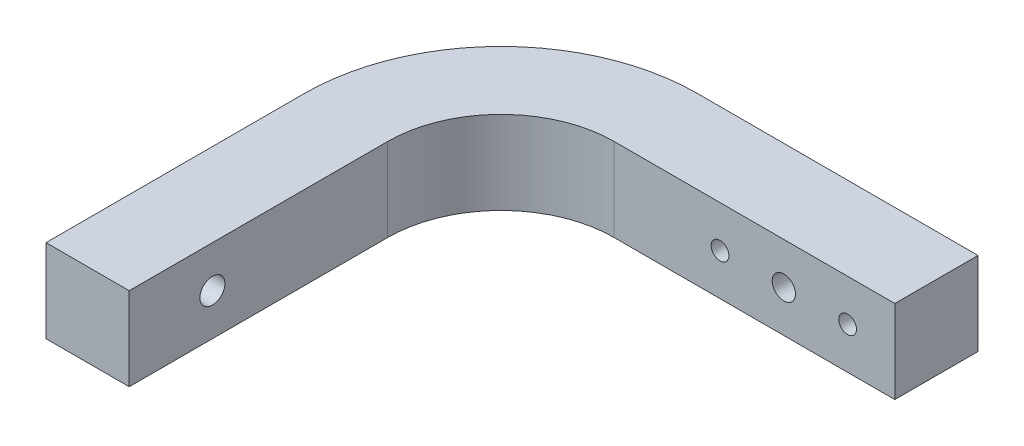
SolidWorks part; units mm, degrees
ref_plane "Front Plane" through (0, 0, 0) normal (0, 0, 1) x (1, 0, 0)
ref_plane "Top Plane" through (0, 0, 0) normal (0, 1, 0) x (1, 0, 0)
ref_plane "Right Plane" through (0, 0, 0) normal (1, 0, 0) x (0, 0, -1)
ref_axis "Z" through (0, 0, -59.2654) along (0, 0, 1)
sketch "Sketch1" plane through (0, 0, 0) normal (0, 1, 0) x (1, 0, 0)
  line L0 (-30.6, 0) -> (30.6, 0) construction
  line L1 (-66, -35.4) -> (-66, -82)
  line L2 (-66, -82) -> (-51, -82)
  line L3 (-51, -82) -> (-51, -35.4)
  line L4 (-30.6, -15) -> (30.6, -15) construction
  line L5 (0, -15) -> (0, 0) construction
  line L6 (51, -82) -> (51, -35.4) construction
  line L7 (66, -82) -> (51, -82) construction
  line L8 (66, -35.4) -> (66, -82) construction
  line L9 (30.6, 0) -> (30.6, -15) construction
  line L10 (20, -15) -> (20, 0)
  line L11 (-30.6, -15) -> (20, -15)
  line L12 (-30.6, 0) -> (20, 0)
  line L13 (0, 59.2654) -> (0, -30.9346) construction
  arc A0 (-30.6, 0) -> (-66, -35.4) centre (-30.6, -35.4) ccw
  arc A1 (-51, -35.4) -> (-30.6, -15) centre (-30.6, -35.4) cw
  arc A2 (51, -35.4) -> (30.6, -15) centre (30.6, -35.4) ccw construction
  arc A3 (30.6, 0) -> (66, -35.4) centre (30.6, -35.4) cw construction
  dimension "D3" = 20.4
  dimension "D1" = 102
  dimension "D2" = 15
  dimension "D4" = 67
  dimension "D5" = 20
extrude "Boss-Extrude1" add sketch "Sketch1" along normal blind 7.5 and the other way blind 7.5
sketch "Sketch2" plane through (-51, 0, 0) normal (-1, 0, 0) x (0, 0, 1)
  line L1 (45.1, 0) -> (-45.1, 0) construction
  line L2 (0, -8.25) -> (0, 8.25) construction
  circle A0 centre (67, 0) radius 2.25
  dimension "D1" = 4.5
  dimension "D2" = 67
extrude "Cut-Extrude1" cut sketch "Sketch2" against normal through all both and the other way through all
ref_axis "Axis2" through (-92.6767, 0, 67) along (1, 0, 0)
sketch "Sketch3" plane through (0, 0, 0) normal (0, 0, -1) x (-1, 0, 0)
  line L0 (-11.5, 0) -> (11.5, 0) construction
  circle A0 centre (0, 0) radius 2.1
  circle A1 centre (-11.5, 0) radius 1.6
  circle A2 centre (11.5, 0) radius 1.6
  dimension "D1" = 4.2
  dimension "D3" = 3.2
  dimension "D2" = 23
extrude "Cut-Extrude2" cut sketch "Sketch3" against normal through all
equation "\"width\"= \"EyeDiameter\" + \"EyeClearance\""
equation "\"prongwidth\"= \"L2Thickness\""
equation "\"D2@Sketch1\"=\"prongwidth\""
equation "\"D3@Sketch1\"=\"width\"/5"
equation "\"pronglength\"= \"BasePlaneDistance\"'model implicitly adds clearance (of prongwidth) to the hole drilled at the baseplanedistance"
equation "\"D4@Sketch1\"=\"pronglength\""
equation "\"D1@Boss-Extrude1\"=\"prongwidth\"/2"
equation "\"D2@Boss-Extrude1\"=\"prongwidth\"/2"
equation "\"lbracket-plane-to-axis\"= \"BasePlaneDistance\""
equation "\"D2@Sketch2\"=\"lbracket-plane-to-axis\""
equation "\"EyeDiameter\" = 100"
equation "\"BasePlaneDistance\" = \"EyeDiameter\"/2+\"L2Thickness\"+\"EyeClearance\""
equation "\"EyeClearance\" = 2"
equation "\"D1@Sketch1\"=\"EyeDiameter\"+\"EyeClearance\""
equation "\"BearingDepth\"= 6"
equation "\"BearingHousingID\"=4.5"
equation "\"BearingFlangeThickness\"= 0.75"
equation "\"BearingFlangeOD\"=7.5"
equation "\"PrinterFilamentThickness\"= 0.1"
equation "\"ApplyPrinterOffset\"= 1'if 1, adjust hole sizes to try and make pressfits work with the 3d printer"
equation "\"L2Thickness\" = 15"
equation "\"L2_ID\" = 20"
equation "\"vx\" = 0"
equation "\"vy\" = 0"
equation "\"vz\" = 100"
equation "\"parametric_end\" = 1"
equation "\"Rw_3_xx\" = -(\"vz\")/sqr((\"vx\")^2 + (\"vz\")^2)"
equation "\"Rw_3_xy\" = 0"
equation "\"Rw_3_xz\" = (\"vx\")/sqr((\"vx\")^2 + (\"vz\")^2)"
equation "\"Rw_3_zx\" = (\"vx\")/sqr((\"vx\")^2 + (\"vy\")^2 + (\"vz\")^2)"
equation "\"Rw_3_zy\" = (\"vy\")/sqr((\"vx\")^2 + (\"vy\")^2 + (\"vz\")^2)"
equation "\"Rw_3_zz\" = (\"vz\")/sqr((\"vx\")^2 + (\"vy\")^2 + (\"vz\")^2)"
equation "\"Rw_3_yx\" = (\"vx\")*(\"vy\")/sqr((\"vx\")^4 + (\"vx\")^2*(\"vy\")^2 + 2*(\"vx\")^2*(\"vz\")^2 + (\"vy\")^2*(\"vz\")^2 + (\"vz\")^4)"
equation "\"Rw_3_yy\" = -sqr((\"vx\")^2 + (\"vz\")^2)/sqr((\"vx\")^2 + (\"vy\")^2 + (\"vz\")^2)"
equation "\"Rw_3_yz\" = (\"vy\")*(\"vz\")/sqr((\"vx\")^4 + (\"vx\")^2*(\"vy\")^2 + 2*(\"vx\")^2*(\"vz\")^2 + (\"vy\")^2*(\"vz\")^2 + (\"vz\")^4)"
equation "\"O2Targx\" = -\"BasePlaneDistance\"*(\"vx\")*(\"vy\")/sqr((\"vx\")^4 + (\"vx\")^2*(\"vy\")^2 + 2*(\"vx\")^2*(\"vz\")^2 + (\"vy\")^2*(\"vz\")^2 + (\"vz\")^4)"
equation "\"O2Targy\" = \"BasePlaneDistance\"*sqr((\"vx\")^2 + (\"vz\")^2)/sqr((\"vx\")^2 + (\"vy\")^2 + (\"vz\")^2)"
equation "\"O2Targz\" = -\"BasePlaneDistance\"*(\"vy\")*(\"vz\")/sqr((\"vx\")^4 + (\"vx\")^2*(\"vy\")^2 + 2*(\"vx\")^2*(\"vz\")^2 + (\"vy\")^2*(\"vz\")^2 + (\"vz\")^4)"
equation "\"O2Targx_0\" = -(\"BasePlaneDistance\")*sqr((\"vx\")^2 + (\"vz\")^2)/sqr((\"vx\")^2 + (\"vy\")^2 + (\"vz\")^2)"
equation "\"O2Targy_0\" = -(\"BasePlaneDistance\")*(\"vy\")*(\"vz\")/sqr((\"vx\")^4 + (\"vx\")^2*(\"vy\")^2 + 2*(\"vx\")^2*(\"vz\")^2 + (\"vy\")^2*(\"vz\")^2 + (\"vz\")^4)"
equation "\"O2Targz_0\" = (\"BasePlaneDistance\")*(\"vx\")*(\"vy\")/sqr((\"vx\")^4 + (\"vx\")^2*(\"vy\")^2 + 2*(\"vx\")^2*(\"vz\")^2 + (\"vy\")^2*(\"vz\")^2 + (\"vz\")^4) + (\"BasePlaneDistance\")"
equation "\"theta2_s1\" = arcsin(((\"BasePlaneDistance\") - (\"O2Targz_0\"))/(\"BasePlaneDistance\")) + pi"
equation "\"theta2_s2\" = -arcsin(((\"BasePlaneDistance\") - (\"O2Targz_0\"))/(\"BasePlaneDistance\"))"
equation "\"theta1_s1\" = arcsin((\"O2Targy_0\")/((\"BasePlaneDistance\")*cos((\"Theta2\")))) + pi"
equation "\"theta1_s2\" = -arcsin((\"O2Targy_0\")/((\"BasePlaneDistance\")*cos((\"Theta2\"))))"
equation "\"theta1_s3\" = -arccos(-(\"O2Targx_0\")/((\"BasePlaneDistance\")*cos((\"Theta2\")))) + 2*pi"
equation "\"theta1_s4\" = arccos(-(\"O2Targx_0\")/((\"BasePlaneDistance\")*cos((\"Theta2\"))))"
equation "\"Theta1\" = \"theta1_s2\" 'so far, theta1_s1 and theta1_s4 have agreed, and they agree with the sw constraint solver"
equation "\"Theta2\" = \"theta2_s2\""
equation "\"o2_x\" = -(\"BasePlaneDistance\")*cos((\"Theta1\"))*cos((\"Theta2\"))"
equation "\"o2_y\" = -(\"BasePlaneDistance\")*sin((\"Theta1\"))*cos((\"Theta2\"))"
equation "\"o2_z\" = (\"BasePlaneDistance\")*(sin((\"Theta2\")) + 1)"
equation "\"o1_x\" = (\"BasePlaneDistance\")*sin((\"Theta1\"))"
equation "\"o1_y\" = -(\"BasePlaneDistance\")*cos((\"Theta1\"))"
equation "\"o1_z\" = (\"BasePlaneDistance\")"
equation "\"Actuator1_Theta\" = atn(\"vx\"/\"vz\") 'ik solution for the single link joint"
equation "\"Actuator2_Theta\" = \"Theta1\"  'ik solution for the double link joint"
equation "\"MotorBaseThickness\" = 3 "
equation "\"BaseThickness\" = 3 "
equation "\"EncoderToMagnetAirgap\" = 1 'Encoder to magnet airgap"
equation "\"EncoderHeight\" = 1.192  'Height of the encoder"
equation "\"MagnetThickness\" = 0.5  'Magnet thickness"
equation "\"pcb_thickness\" = 1.6  'Thickness of the PCB"
equation "\"pcb_outer_diameter\" = 32 'the OD of the pcb"
equation "\"shaft_diameter\" = 4"
equation "\"D1@Sketch2\"=\"shaft_diameter\"*1.125"
